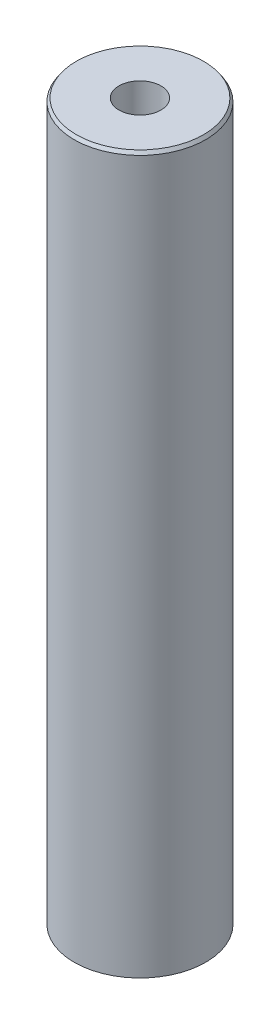
SolidWorks part; units mm, degrees
ref_plane "Front Plane" through (0, 0, 0) normal (0, 0, 1) x (1, 0, 0)
ref_plane "Top Plane" through (0, 0, 0) normal (0, 1, 0) x (1, 0, 0)
ref_plane "Right Plane" through (0, 0, 0) normal (1, 0, 0) x (0, 0, -1)
sketch "Sketch1" plane through (0, 0, 0) normal (0, 1, 0) x (1, 0, 0)
  circle A0 centre (0, 0) radius 55
  dimension "SHAFT_OD" = 110
extrude "Boss-Extrude1" add sketch "Sketch1" along normal blind 600
sketch "Sketch2" plane through (0, 0, 0) normal (0, 1, 0) x (1, 0, 0)
  circle A0 centre (0, 0) radius 17.5492
  dimension "BORE_D" = 35.0985
extrude "Cut-Extrude1" cut sketch "Sketch2" along normal through all
chamfer "Chamfer1" distance 2.7088 angle 33.702 2 edges at (0, 600, 55) (0, 0, 55) first distance on face at (0, 600, 55) first distance on face at (0, 0, 17.5492)
